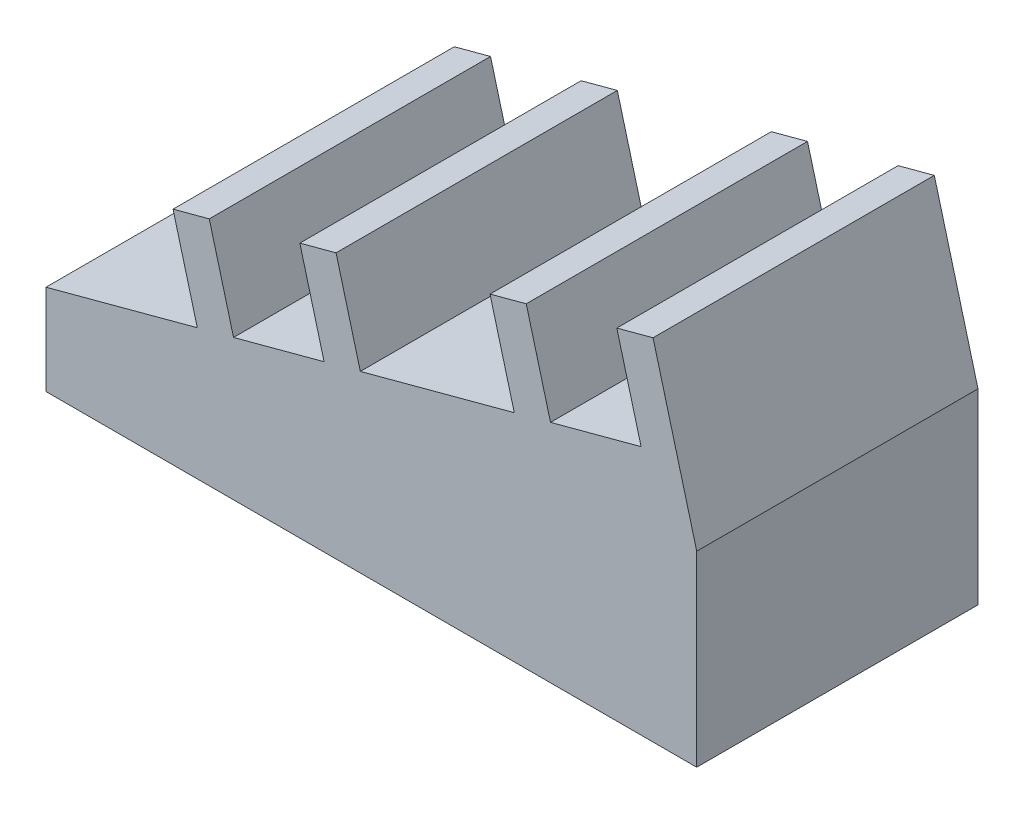
SolidWorks part; units mm, degrees
ref_plane "Front Plane" through (0, 0, 0) normal (0, 0, 1) x (1, 0, 0)
ref_plane "Top Plane" through (0, 0, 0) normal (0, 1, 0) x (1, 0, 0)
ref_plane "Right Plane" through (0, 0, 0) normal (1, 0, 0) x (0, 0, -1)
sketch "Sketch1" plane through (0, 0, 0) normal (0, 0, 1) x (1, 0, 0)
  line L0 (25.0915, 14.6214) -> (15.4322, 12.0332)
  line L1 (15.4322, 12.0332) -> (12.844, 21.6925)
  line L2 (12.844, 21.6925) -> (8.9803, 20.6572)
  line L3 (8.9803, 20.6572) -> (11.5685, 10.9979)
  line L4 (11.5685, 10.9979) -> (-4.8522, 6.598)
  line L5 (-4.8522, 6.598) -> (-7.4404, 16.2573)
  line L6 (-7.4404, 16.2573) -> (-11.3041, 15.222)
  line L7 (-11.3041, 15.222) -> (-8.7159, 5.5627)
  line L8 (-8.7159, 5.5627) -> (-18.3752, 2.9745)
  line L9 (-18.3752, 2.9745) -> (-20.9634, 12.6338)
  line L10 (-20.9634, 12.6338) -> (-24.8271, 11.5985)
  line L11 (-24.8271, 11.5985) -> (-22.2389, 1.9393)
  line L12 (-22.2389, 1.9393) -> (-38.3752, -2.3845)
  line L13 (-38.3752, -2.3845) -> (-38.3752, -12.0255)
  line L14 (-38.3752, -12.0255) -> (31.0257, -12.0255)
  line L15 (31.0257, -12.0255) -> (31.0257, 7.9293)
  line L16 (31.0257, 7.9293) -> (26.367, 25.3159)
  line L17 (26.367, 25.3159) -> (22.5033, 24.2806)
  line L18 (22.5033, 24.2806) -> (25.0915, 14.6214)
  point P18 (16.5607, 25.0382)
  point P20 (0, 0)
  point P21 (25.9682, 14.8563)
  point P22 (30.1194, 7.4481)
  point P23 (0, 0)
  dimension "D1" = 25
  dimension "D2" = 4
  dimension "D3" = 10
  dimension "D4" = 15
  dimension "D5" = 15
  dimension "D6" = 8
  dimension "D7" = 25
  dimension "D8" = 10
extrude "Boss-Extrude1" add sketch "Sketch1" along normal blind 30
sketch "Sketch2" plane through (30.9297, 8.2876, 0) normal (0.9659, 0.2588, 0) x (0, 0, -1)
  line L0 (-15, 17.629) -> (-15, 57.4203) construction
  line L1 (-30, 17.629) -> (0, 17.629) construction
  line L2 (-24.6402, 22.4203) -> (-3.3863, 22.4203) construction
  circle A0 centre (-15, 57.4203) radius 32.9
  circle A1 centre (-24.6402, 22.4203) radius 1.9419
  circle A2 centre (-3.3863, 22.4203) radius 1.364
  point P1 (-15, 57.4203)
  point P10 (-15, 49.4165)
  dimension "D1" = 65.8
  dimension "D2" = 35
